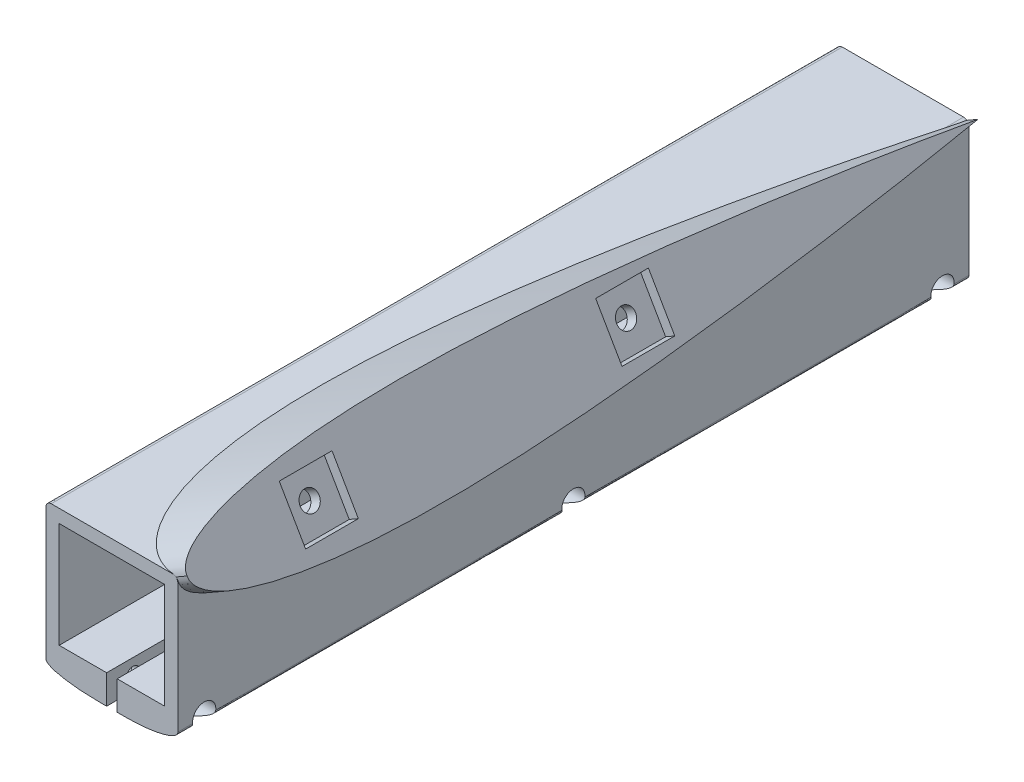
SolidWorks part; units mm, degrees
note: The reader was unsure of these and kept them because the rebuilt part matched: shared geometry of "Sketch5<3>".
material "20% Eyballed PLA"
ref_plane "Front Plane" through (0, 0, 0) normal (0, 0, 1) x (1, 0, 0)
ref_plane "Top Plane" through (0, 0, 0) normal (0, 1, 0) x (1, 0, 0)
ref_plane "Right Plane" through (0, 0, 0) normal (1, 0, 0) x (0, 0, -1)
sketch "Sketch1" plane through (0, 0, 0) normal (0, 0, 1) x (1, 0, 0)
  line L1 (-12.5, 14) -> (12.5, 14)
  line L2 (-12.5, 14) -> (-12.5, -14)
  line L3 (-12.5, -14) -> (12.5, -14)
  line L4 (12.5, 14) -> (12.5, -14)
  line L5 (-12.5, 14) -> (12.5, -14) construction
  line L6 (-12.5, -14) -> (12.5, 14) construction
  point P0 (0, 0)
  dimension "D1" = 28
  dimension "D2" = 25
extrude "Boss-Extrude1" add sketch "Sketch1" along normal blind 150 contours L2 L3 L4 L1
ref_plane "Plane2" through (15.4372, 8.9127, 0) normal (-0.866, -0.5, 0) x (0, 0, -1)
sketch "Sketch3" plane through (15.4372, 8.9127, 0) normal (-0.866, -0.5, 0) x (0, 0, -1)
  line L0 (-150, -5.8744) -> (0, -5.8744) construction
  line L1 (-150, -5.8744) -> (0, -5.8744)
fillet "Fillet1" radius 1 2 edges at (12.5, 14, 75) (-12.5, 14, 75)
sketch "Sketch5" plane through (15.4372, 8.9127, 0) normal (-0.866, -0.5, 0) x (0, 0, -1)
  line L0 (-150, -5.8744) -> (-149, -5.8731) construction
  line L1 (-150, -5.8744) -> (0, -5.8744) construction
  spline S0 degree 3 poles (-150, -5.8744) (-149.9999, -5.8758) (-149.9996, -5.8787) (-149.9977, -5.883) (-149.9947, -5.8871) (-149.9905, -5.8911) (-149.9852, -5.8949) (-149.9788, -5.8986) (-149.9713, -5.9022) (-149.9627, -5.9056) (-149.9531, -5.9089) (-149.9423, -5.912) (-149.9261, -5.9161) (-149.9033, -5.9206) (-149.873, -5.925) (-149.8394, -5.9286) (-149.8025, -5.9313) (-149.7556, -5.9333) (-149.6981, -5.9339) (-149.6303, -5.9327) (-149.5516, -5.9294) (-149.464, -5.9238) (-149.3701, -5.9161) (-149.2747, -5.9069) (-149.1791, -5.8964) (-149.0895, -5.8854) (-149.0305, -5.8774) (-149.0033, -5.8736) (-149.0002, -5.8731) (-149, -5.8731) knots 0 0 0 0 0.004218 0.008652 0.013562 0.019137 0.0255 0.032726 0.040862 0.04993 0.05994 0.070892 0.082777 0.109286 0.139301 0.172602 0.208924 0.247965 0.310881 0.377906 0.447679 0.542484 0.636087 0.724985 0.82444 0.919093 0.990775 0.999422 1 1 1 1 construction
  spline S2 degree 3 poles (-150, -5.8744) (-149.9999, -5.8729) (-149.9996, -5.87) (-149.9977, -5.8657) (-149.9947, -5.8616) (-149.9906, -5.8576) (-149.9853, -5.8538) (-149.9789, -5.85) (-149.9714, -5.8465) (-149.9628, -5.843) (-149.9532, -5.8397) (-149.9424, -5.8366) (-149.9262, -5.8324) (-149.9034, -5.8279) (-149.8732, -5.8233) (-149.8395, -5.8197) (-149.8027, -5.817) (-149.7557, -5.8148) (-149.6983, -5.814) (-149.6304, -5.8151) (-149.5518, -5.8181) (-149.4642, -5.8235) (-149.3702, -5.831) (-149.2748, -5.84) (-149.1792, -5.8502) (-149.0895, -5.861) (-149.0305, -5.8688) (-149.0033, -5.8726) (-149.0002, -5.8731) (-149, -5.8731) knots 0 0 0 0 0.004218 0.008652 0.013562 0.019137 0.0255 0.032726 0.040862 0.04993 0.05994 0.070892 0.082777 0.109286 0.139301 0.172602 0.208924 0.247965 0.310881 0.377906 0.447679 0.542484 0.636087 0.724985 0.82444 0.919093 0.990775 0.999422 1 1 1 1 construction
  spline S3 degree 3 poles (-150, -5.8744) (-149.9823, -5.6587) (-149.9459, -5.2164) (-149.6568, -4.5755) (-149.2065, -3.9589) (-148.5814, -3.3639) (-147.7896, -2.7885) (-146.8302, -2.2321) (-145.7052, -1.6952) (-144.4166, -1.1792) (-142.9668, -0.6856) (-141.359, -0.2159) (-138.9191, 0.3985) (-135.4976, 1.0811) (-130.9667, 1.7534) (-125.9153, 2.2951) (-120.3897, 2.699) (-113.3466, 3.0098) (-104.7314, 3.1201) (-94.5508, 2.9496) (-82.7528, 2.4722) (-69.6159, 1.6505) (-55.5249, 0.507) (-41.2158, -0.8587) (-26.8721, -2.4131) (-13.4209, -4.0462) (-4.5792, -5.2296) (-0.4948, -5.8043) (-0.0292, -5.8702) (0, -5.8744) knots 0 0 0 0 0.004218 0.008652 0.013562 0.019137 0.0255 0.032726 0.040862 0.04993 0.05994 0.070892 0.082777 0.109286 0.139301 0.172602 0.208924 0.247965 0.310881 0.377906 0.447679 0.542484 0.636087 0.724985 0.82444 0.919093 0.990775 0.999422 1 1 1 1
  spline S4 degree 3 poles (-150, -5.8744) (-149.9823, -6.09) (-149.9459, -6.5323) (-149.6568, -7.1732) (-149.2065, -7.7898) (-148.5814, -8.3848) (-147.7896, -8.9602) (-146.8302, -9.5166) (-145.7052, -10.0535) (-144.4166, -10.5695) (-142.9668, -11.0631) (-141.359, -11.5328) (-138.9191, -12.1472) (-135.4976, -12.8298) (-130.9667, -13.5021) (-125.9153, -14.0438) (-120.3897, -14.4477) (-113.3466, -14.7586) (-104.7314, -14.8688) (-94.5508, -14.6983) (-82.7528, -14.2209) (-69.6159, -13.3992) (-55.5249, -12.2557) (-41.2158, -10.89) (-26.8721, -9.3357) (-13.4209, -7.7026) (-4.5792, -6.5192) (-0.4948, -5.9444) (-0.0292, -5.8785) (0, -5.8744) knots 0 0 0 0 0.004218 0.008652 0.013562 0.019137 0.0255 0.032726 0.040862 0.04993 0.05994 0.070892 0.082777 0.109286 0.139301 0.172602 0.208924 0.247965 0.310881 0.377906 0.447679 0.542484 0.636087 0.724985 0.82444 0.919093 0.990775 0.999422 1 1 1 1
  dimension "D1" = 150
extrude "Boss-Extrude2" add sketch "Sketch5" along normal blind 20
sketch "Sketch6" plane through (0, 0, 0) normal (0, 0, 1) x (1, 0, 0)
  line L0 (-11.5, 14) -> (11.5, 14) construction
  line L1 (10, 11.5) -> (-10, 11.5)
  line L2 (10, 11.5) -> (10, -8.5)
  line L3 (10, -8.5) -> (-10, -8.5)
  line L4 (-10, 11.5) -> (-10, -8.5)
  line L6 (-12.5, 13) -> (-12.5, -14) construction
  line L7 (12.5, 13) -> (12.5, -14) construction
  dimension "D1" = 2.5
  dimension "D2" = 20
  dimension "D3" = 2.5
  dimension "D4" = 2.5
extrude "Cut-Extrude1" cut sketch "Sketch6" along normal blind 150
sketch "Sketch7" plane through (15.4372, 8.9127, 0) normal (-0.866, -0.5, 0) x (0, 0, -1)
  line L0 (0, -5.8744) -> (-150, -5.8744) construction
  line L1 (-130, -0.8744) -> (-120, -0.8744)
  line L2 (-130, -0.8744) -> (-130, -10.8744)
  line L3 (-130, -10.8744) -> (-120, -10.8744)
  line L4 (-120, -0.8744) -> (-120, -10.8744)
  line L7 (-70, -0.8744) -> (-60, -0.8744)
  line L8 (-70, -0.8744) -> (-70, -10.8744)
  line L9 (-70, -10.8744) -> (-60, -10.8744)
  line L10 (-60, -0.8744) -> (-60, -10.8744)
  spline S2 degree 3 poles (-3081.496, -640.596) (-84.453, 27.9245) (-153.8716, 2.1706) (-149.6568, -7.1732) (-149.2065, -7.7898) (-148.5814, -8.3848) (-147.7896, -8.9602) (-146.8302, -9.5166) (-145.7052, -10.0535) (-144.4166, -10.5695) (-142.9668, -11.0631) (-141.359, -11.5328) (-138.9191, -12.1472) (-135.4976, -12.8298) (-130.9667, -13.5021) (-125.9153, -14.0438) (-120.3897, -14.4477) (-113.3466, -14.7586) (-104.7314, -14.8688) (-94.5508, -14.6983) (-82.7528, -14.2209) (-69.6159, -13.3992) (-55.5249, -12.2557) (-41.2158, -10.89) (-26.8721, -9.3357) (-13.4209, -7.7026) (-4.5792, -6.5192) (35.9134, -0.821) (72.4417, 6.8082) (529.5049, -2957.4363) knots -0.184171 -0.184171 -0.184171 -0.184171 0.004218 0.008652 0.013562 0.019137 0.0255 0.032726 0.040862 0.04993 0.05994 0.070892 0.082777 0.109286 0.139301 0.172602 0.208924 0.247965 0.310881 0.377906 0.447679 0.542484 0.636087 0.724985 0.82444 0.919093 0.990775 0.999422 1.721217 1.721217 1.721217 1.721217 only from (-150, -5.8744) to (0, -5.8744)
  spline S3 degree 3 poles (529.5133, 2945.7427) (72.4421, -18.557) (35.9137, -10.9277) (-4.5792, -5.2296) (-13.4209, -4.0462) (-26.8721, -2.4131) (-41.2158, -0.8587) (-55.5249, 0.507) (-69.6159, 1.6505) (-82.7528, 2.4722) (-94.5508, 2.9496) (-104.7314, 3.1201) (-113.3466, 3.0098) (-120.3897, 2.699) (-125.9153, 2.2951) (-130.9667, 1.7534) (-135.4976, 1.0811) (-138.9191, 0.3985) (-141.359, -0.2159) (-142.9668, -0.6856) (-144.4166, -1.1792) (-145.7052, -1.6952) (-146.8302, -2.2321) (-147.7896, -2.7885) (-148.5814, -3.3639) (-149.2065, -3.9589) (-149.6568, -4.5755) (-153.8716, -13.9194) (-84.4521, -39.6735) (-3081.5528, 628.8599) knots -0.721222 -0.721222 -0.721222 -0.721222 0.000578 0.009225 0.080907 0.17556 0.275015 0.363913 0.457516 0.552321 0.622094 0.689119 0.752035 0.791076 0.827398 0.860699 0.890714 0.917223 0.929108 0.94006 0.95007 0.959138 0.967274 0.9745 0.980863 0.986438 0.991348 0.995782 1.184172 1.184172 1.184172 1.184172 only from (0, -5.8744) to (-150, -5.8744)
  spline S4 degree 3 poles (-150, -5.8744) (-149.9823, -6.09) (-149.9459, -6.5323) (-149.6568, -7.1732) (-149.2065, -7.7898) (-148.5814, -8.3848) (-147.7896, -8.9602) (-146.8302, -9.5166) (-145.7052, -10.0535) (-144.4166, -10.5695) (-142.9668, -11.0631) (-141.359, -11.5328) (-138.9191, -12.1472) (-135.4976, -12.8298) (-130.9667, -13.5021) (-125.9153, -14.0438) (-120.3897, -14.4477) (-113.3466, -14.7586) (-104.7314, -14.8688) (-94.5508, -14.6983) (-82.7528, -14.2209) (-69.6159, -13.3992) (-55.5249, -12.2557) (-41.2158, -10.89) (-26.8721, -9.3357) (-13.4209, -7.7026) (-4.5792, -6.5192) (-0.4948, -5.9444) (-0.0292, -5.8785) (0, -5.8744) knots 0 0 0 0 0.004218 0.008652 0.013562 0.019137 0.0255 0.032726 0.040862 0.04993 0.05994 0.070892 0.082777 0.109286 0.139301 0.172602 0.208924 0.247965 0.310881 0.377906 0.447679 0.542484 0.636087 0.724985 0.82444 0.919093 0.990775 0.999422 1 1 1 1 construction
  spline S5 degree 3 poles (0, -5.8744) (-0.0292, -5.8702) (-0.4948, -5.8043) (-4.5792, -5.2296) (-13.4209, -4.0462) (-26.8721, -2.4131) (-41.2158, -0.8587) (-55.5249, 0.507) (-69.6159, 1.6505) (-82.7528, 2.4722) (-94.5508, 2.9496) (-104.7314, 3.1201) (-113.3466, 3.0098) (-120.3897, 2.699) (-125.9153, 2.2951) (-130.9667, 1.7534) (-135.4976, 1.0811) (-138.9191, 0.3985) (-141.359, -0.2159) (-142.9668, -0.6856) (-144.4166, -1.1792) (-145.7052, -1.6952) (-146.8302, -2.2321) (-147.7896, -2.7885) (-148.5814, -3.3639) (-149.2065, -3.9589) (-149.6568, -4.5755) (-149.9459, -5.2164) (-149.9823, -5.6587) (-150, -5.8744) knots 0 0 0 0 0.000578 0.009225 0.080907 0.17556 0.275015 0.363913 0.457516 0.552321 0.622094 0.689119 0.752035 0.791076 0.827398 0.860699 0.890714 0.917223 0.929108 0.94006 0.95007 0.959138 0.967274 0.9745 0.980863 0.986438 0.991348 0.995782 1 1 1 1 construction
  point P4 (-120, -5.8744)
  point P5 (-70, -5.8744)
  dimension "D5" = 0
  dimension "D1" = 10
  dimension "D2" = 20
  dimension "D3" = 10
  dimension "D4" = 50
ref_plane "Plane3" through (12.4796, 7.2051, 0) normal (-0.866, -0.5, 0) x (0, 0, 1)
sketch "Sketch9" plane through (12.4796, 7.2051, 0) normal (-0.866, -0.5, 0) x (0, 0, 1)
  line L0 (70, 0.8744) -> (60, 0.8744) construction
  line L1 (60, 0.8744) -> (60, 10.8744) construction
  line L2 (70, 10.8744) -> (60, 10.8744) construction
  line L3 (70, 0.8744) -> (70, 10.8744) construction
  line L4 (120, 0.8744) -> (120, 10.8744) construction
  line L5 (130, 0.8744) -> (130, 10.8744) construction
  line L6 (130, 0.8744) -> (120, 0.8744) construction
  line L7 (130, 10.8744) -> (120, 10.8744) construction
  line L8 (70, 0.8744) -> (60, 0.8744)
  line L9 (60, 0.8744) -> (60, 10.8744)
  line L10 (70, 10.8744) -> (60, 10.8744)
  line L11 (70, 0.8744) -> (70, 10.8744)
  line L12 (120, 0.8744) -> (120, 10.8744)
  line L13 (130, 0.8744) -> (130, 10.8744)
  line L14 (130, 0.8744) -> (120, 0.8744)
  line L15 (130, 10.8744) -> (120, 10.8744)
extrude "Cut-Extrude3" cut sketch "Sketch9" along normal up to surface (28.3392 mm away)
hole_wizard "CSK for M3 Flat Head Machine Screw1" positions "Sketch30" profile "Sketch31" countersink size "M3" standard "ANSI Metric" end condition through all
sketch "Sketch30" plane through (12.4796, 7.2051, 0) normal (-0.866, -0.5, 0) x (0, 0, 1)
  line L0 (130, 10.8744) -> (120, 10.8744) construction
  line L1 (120, 10.8744) -> (120, 4.9593) construction
  line L2 (70, 0.8744) -> (70, 10.8744) construction
  line L3 (70, 0.8744) -> (60, 0.8744) construction
  point P0 (125, 5.8744)
  point P2 (65, 5.8744)
  dimension "D1" = 5
  dimension "D2" = 5
  dimension "D3" = 5
  dimension "D4" = 5
sketch "Sketch31" plane through (9.5425, 12.2925, 125) normal (0, 0, 1) x (0.5, -0.866, 0)
  line L0 (0, 0) -> (0, 11.6643)
  line L1 (0, 11.6643) -> (1.8, 11.6643)
  line L2 (1.8, 11.6643) -> (1.8, 1.35)
  line L3 (1.8, 1.35) -> (3.15, 0)
  line L5 (3.15, 0) -> (0, 0)
  line L6 (-1.8, 1.35) -> (-3.15, 0) construction
  line L11 (0, -6.35) -> (0, 107.95) construction
  dimension "Thru Hole Dia." = 3.6
  dimension "Thru Hole Depth" = 11.6643
  dimension "Near C'Sink Dia." = 6.3
  dimension "Near C'Sink Angle" = 90
extrude "Boss-Extrude3" add sketch "Sketch5<3>" against normal blind 2
sketch "Sketch5<3>" plane through (15.4372, 8.9127, 0) normal (-0.866, -0.5, 0) x (0, 0, -1) same geometry as "Sketch5"
extrude "Cut-Extrude6" cut sketch "Sketch7" against normal blind 2
fillet "Fillet2" radius 2 3 edges at (0, -14, 150) (0, -14, 0) (-12.5, -14, 75)
fillet "Fillet3" radius 2.5 1 edges at (12.5, -14, 75)
sketch "Sketch32" plane through (0, 0, 0) normal (0, 0, -1) x (-1, 0, 0)
  line L0 (0, -8.5) -> (0, -14) construction
  line L1 (10, -8.5) -> (-10, -8.5) construction
  line L2 (2.5, -14) -> (-2.5, -14) construction
  line L4 (-1, -8.5) -> (1, -8.5)
  line L5 (-1, -8.5) -> (-1, -14)
  line L6 (-1, -14) -> (1, -14)
  line L7 (1, -8.5) -> (1, -14)
  line L8 (-1, -8.5) -> (1, -14) construction
  line L9 (-1, -14) -> (1, -8.5) construction
  point P6 (0, -11.25)
  dimension "D1" = 2
extrude "Cut-Extrude7" cut sketch "Sketch32" against normal up to vertex
hole_wizard "CSK for M2 Countersunk Flat Head Screw1" positions "3DSketch1" profile "Sketch34" countersink size "M2" standard "ISO"
sketch3d "3DSketch1"
  line L0 (12.5, -11.5, 150) -> (12.5, -11.5, 0) construction
  line L1 (12.5, 13, 0) -> (12.5, -11.5, 0) construction
  point P15 (12.5, -11.25, 5)
  point P17 (12.5, -11.25, 75)
  point P19 (12.5, -11.25, 145)
  dimension "D1" = 0.25
  dimension "D3" = 0.25
  dimension "D2" = 0.25
  dimension "D4" = 5
  dimension "D5" = 70
  dimension "D6" = 70
sketch "Sketch34" plane through (12.5, -11.25, 5) normal (0, 1, 0) x (0, 0, -1)
  line L0 (0, 0) -> (0, 35.7811)
  line L1 (0, 35.7811) -> (1.3, 35)
  line L2 (1.3, 35) -> (1.3, 9.9)
  line L3 (1.3, 9.9) -> (2.2, 9)
  line L4 (2.2, 9) -> (2.2, 0)
  line L6 (2.2, 0) -> (0, 0)
  line L7 (-1.3, 9.9) -> (-2.2, 9) construction
  line L10 (0, 35.7811) -> (-1.3, 35) construction
  line L11 (0, -6.35) -> (0, 107.95) construction
  dimension "Hole Dia." = 2.6
  dimension "Hole Depth" = 35
  dimension "C'Sink Dia." = 4.4
  dimension "C'Sink Angle" = 90
  dimension "Drill Angle" = 118
  dimension "Head Clearance" = 9
sketch "Sketch41" plane through (-12.5, 0, 0) normal (-1, 0, 0) x (0, 0, 1)
  line L0 (3.7, -11.25) -> (6.3, -11.25) construction
  line L2 (7.3094, -11.25) -> (6.1547, -9.25)
  line L3 (6.1547, -9.25) -> (3.8453, -9.25)
  line L4 (3.8453, -9.25) -> (2.6906, -11.25)
  line L5 (2.6906, -11.25) -> (3.8453, -13.25)
  line L6 (3.8453, -13.25) -> (6.1547, -13.25)
  line L7 (6.1547, -13.25) -> (7.3094, -11.25)
  line L8 (77.3094, -11.25) -> (76.1547, -9.25)
  line L9 (76.1547, -9.25) -> (73.8453, -9.25)
  line L10 (73.8453, -9.25) -> (72.6906, -11.25)
  line L11 (72.6906, -11.25) -> (73.8453, -13.25)
  line L12 (73.8453, -13.25) -> (76.1547, -13.25)
  line L13 (76.1547, -13.25) -> (77.3094, -11.25)
  line L14 (147.3094, -11.25) -> (146.1547, -9.25)
  line L15 (146.1547, -9.25) -> (143.8453, -9.25)
  line L16 (143.8453, -9.25) -> (142.6906, -11.25)
  line L17 (142.6906, -11.25) -> (143.8453, -13.25)
  line L18 (143.8453, -13.25) -> (146.1547, -13.25)
  line L19 (146.1547, -13.25) -> (147.3094, -11.25)
  arc A0 (6.0618, -12) -> (3.9382, -12) centre (5, -11.25) ccw construction
  circle A1 centre (5, -11.25) radius 2 construction
  circle A2 centre (75, -11.25) radius 2 construction
  circle A3 centre (145, -11.25) radius 2 construction
  dimension "D1" = 4
  dimension "D2" = 4
  dimension "D3" = 4
extrude "Cut-Extrude8" cut sketch "Sketch41" against normal blind 10
